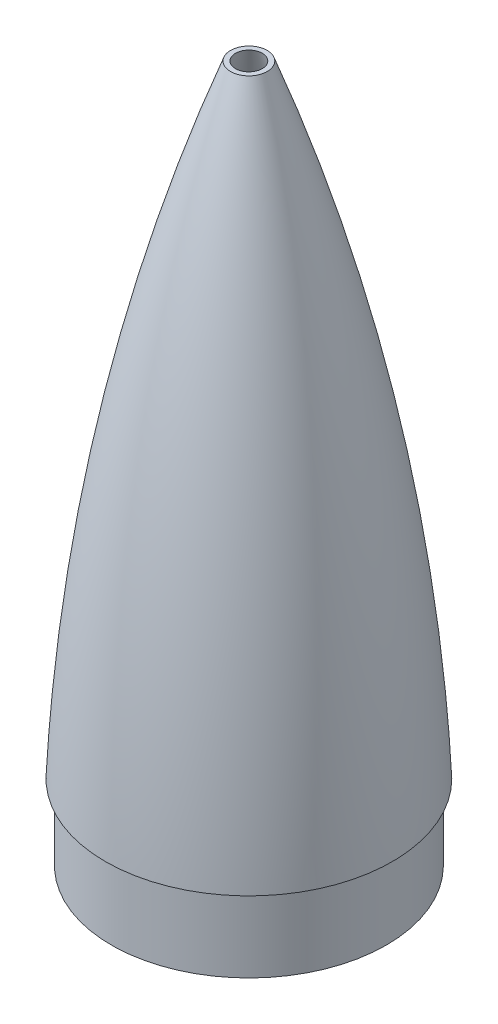
SolidWorks part; units mm, degrees
material "PVB"
ref_plane "Front Plane" through (0, 0, 0) normal (0, 0, 1) x (1, 0, 0)
ref_plane "Top Plane" through (0, 0, 0) normal (0, 1, 0) x (1, 0, 0)
ref_plane "Right Plane" through (0, 0, 0) normal (1, 0, 0) x (0, 0, -1)
sketch "Sketch2" plane through (0, 0, 0) normal (0, 0, 1) x (1, 0, 0)
  line L0 (0, 0) -> (0, 355.6) construction
  line L1 (-76.2, 0) -> (-69.85, 0)
  line L2 (0, 355.6) -> (0, 350.52)
  arc A0 (0, 355.6) -> (-76.2, 0) centre (1016.1023, -48.1005) ccw
  arc A1 (0, 350.52) -> (-69.85, 0) centre (1135.4329, -57.9635) ccw
  dimension "D1" = 355.6
  dimension "D2" = 5.08
  dimension "D3" = 76.2
  dimension "D4" = 6.35
revolve "Revolve1" add sketch "Sketch2" angle 360 about L2
ref_plane "Plane2" through (0, 381, 0) normal (0, 1, 0) x (1, 0, 0)
sketch "Sketch7" plane through (0, 381, 0) normal (0, 1, 0) x (1, 0, 0)
  circle A0 centre (0, 0) radius 317.5
  dimension "D1" = 635
extrude "Cut-Extrude2" cut sketch "Sketch7" against normal blind 50.8
sketch "Sketch8" plane through (0, 0, 0) normal (0, -1, 0) x (1, 0, 0)
  circle A0 centre (0, 0) radius 69.85
  circle A1 centre (0, 0) radius 73.025
  dimension "D1" = 146.05
extrude "Boss-Extrude1" add sketch "Sketch8" along normal blind 40
